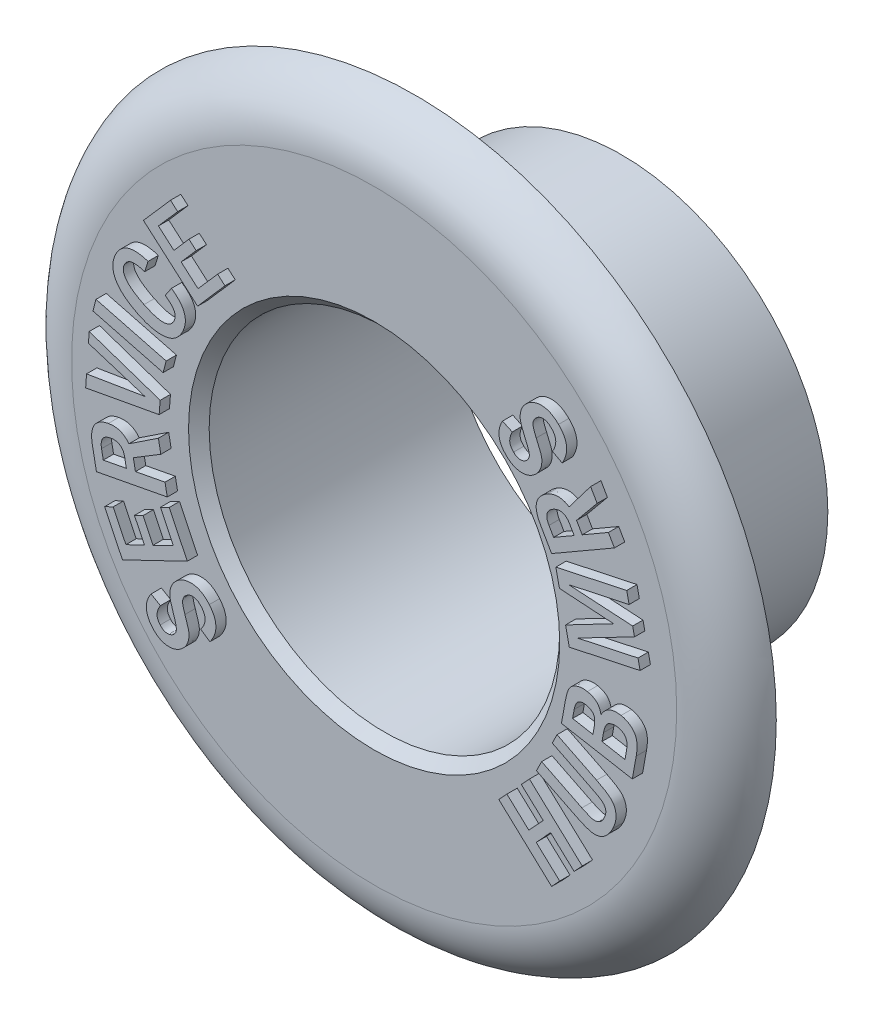
SolidWorks part; units mm, degrees
ref_plane "Plan de face" through (0, 0, 0) normal (0, 0, 1) x (1, 0, 0)
ref_plane "Plan de dessus" through (0, 0, 0) normal (0, 1, 0) x (1, 0, 0)
ref_plane "Plan de droite" through (0, 0, 0) normal (1, 0, 0) x (0, 0, -1)
sketch "Esquisse1" plane through (0, 0, 0) normal (0, 0, 1) x (1, 0, 0)
  circle A0 centre (0, 0) radius 8.5
  circle A1 centre (0, 0) radius 10
  dimension "D1" = 17
  dimension "D2" = 20
extrude "Boss.-Extru.1" add sketch "Esquisse1" along normal blind 10
sketch "Esquisse2" plane through (0, 0, 10) normal (0, 0, 1) x (1, 0, 0)
  circle A0 centre (0, 0) radius 17.5
  circle A1 centre (0, 0) radius 8.5
  dimension "D1" = 35
  dimension "D2" = 17
extrude "Boss.-Extru.2" add sketch "Esquisse2" along normal blind 2
fillet "Congé1" radius 3 1 edges at (17.5, 0, 12)
chamfer "Chanfrein1" distance 0.5 angle 45 1 edges at (8.5, 0, 12)
sketch "Esquisse3" plane through (0, 0, 12) normal (0, 0, 1) x (1, 0, 0)
  line L0 (0, 0) -> (14.6716, 0) construction
  circle A0 centre (0, 0) radius 10 construction
  circle A1 centre (0, 0) radius 13.5 construction
  circle A2 centre (0, 0) radius 14.6716 construction
  text T0 "SERVICE" font "Franklin Gothic Medium Cond" height 3.5
  text T1 "H U B " font "Franklin Gothic Medium Cond" height 3.5
  text T2 " M R S" font "Franklin Gothic Medium Cond" height 3.5
  dimension "D1" = 27
  dimension "D2" = 20
extrude "Boss.-Extru.3" add sketch "Esquisse3" along normal blind 0.5
